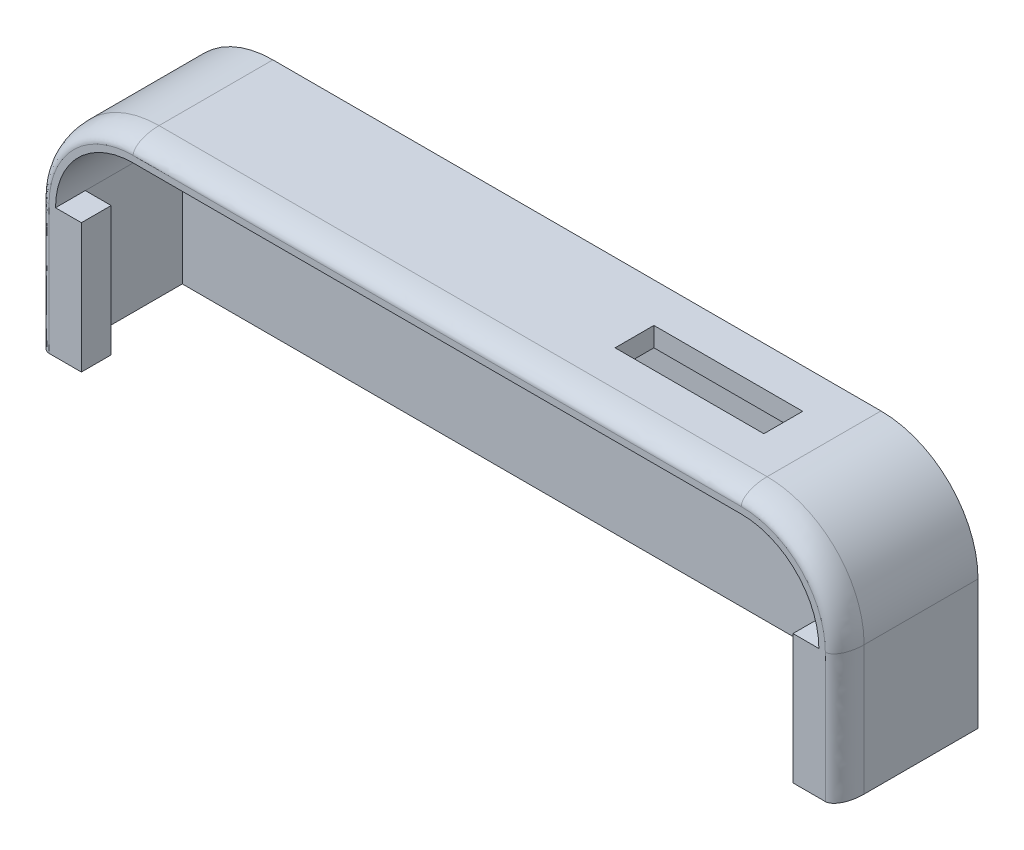
SolidWorks part; units mm, degrees
ref_plane "Front Plane" through (0, 0, 0) normal (0, 0, 1) x (1, 0, 0)
ref_plane "Top Plane" through (0, 0, 0) normal (0, 1, 0) x (1, 0, 0)
ref_plane "Right Plane" through (0, 0, 0) normal (1, 0, 0) x (0, 0, -1)
sketch "Sketch1" plane through (0, 0, 0) normal (0, 0, 1) x (1, 0, 0)
  line L0 (31, 17.5) -> (31, 0)
  line L1 (0, 0) -> (62, 0)
  line L2 (0, 0) -> (0, 10)
  line L3 (7.5, 17.5) -> (54.5, 17.5)
  line L4 (62, 0) -> (62, 10)
  line L5 (7.5, 16) -> (54.5, 16)
  line L9 (1.5, 0) -> (1.5, 10)
  line L12 (60.5, 10) -> (60.5, 0)
  arc A0 (0, 10) -> (7.5, 17.5) centre (7.5, 10) cw
  arc A1 (62, 10) -> (54.5, 17.5) centre (54.5, 10) ccw
  arc A2 (1.5, 10) -> (7.5, 16) centre (7.5, 10) cw
  arc A3 (60.5, 10) -> (54.5, 16) centre (54.5, 10) ccw
  dimension "D5" = 1.5
extrude "Boss-Extrude1" add sketch "Sketch1" along normal blind 10.8 contours L9 A2 L5 L0 L3 A0 L2 L1 | A3 L12 L1 L4 A1 L3 L0 L5 region at (42.75, 17.144, 0) region at (30.644, 16.75, 0)
sketch "Sketch2" plane through (0, 0, 0) normal (0, 0, -1) x (-1, 0, 0)
  line L0 (-1.5, 0) -> (-1.5, 10)
  line L1 (-7.5, 16) -> (-54.5, 16)
  line L2 (-60.5, 0) -> (-60.5, 10)
  line L3 (-60.5, 0) -> (-1.5, 0)
  arc A0 (-1.5, 10) -> (-7.5, 16) centre (-7.5, 10) ccw
  arc A1 (-54.5, 16) -> (-60.5, 10) centre (-54.5, 10) ccw
extrude "Boss-Extrude2" add sketch "Sketch2" against normal blind 1 separate body
combine bodies "Combine1" operation type add bodies to combine 102 101
sketch "Sketch3" plane through (0, 0, 10.8) normal (0, 0, 1) x (1, 0, 0)
  line L0 (0, 0) -> (3.5, 0)
  line L1 (0, 0) -> (0, 10)
  line L2 (0, 0) -> (0, 10) construction
  line L3 (3.5, 0) -> (3.5, 10)
  line L4 (3.5, 10) -> (0, 10)
  line L5 (1.5, 10) -> (1.5, 0)
  line L6 (31, 16) -> (31, -7.5027)
  line L7 (7.5, 16) -> (54.5, 16) construction
  line L8 (60.5, 10) -> (60.5, 0)
  line L9 (62, 0) -> (58.5, 0)
  line L10 (58.5, 10) -> (62, 10)
  line L11 (58.5, 0) -> (58.5, 10)
  line M7 (1.5, 0) -> (1.5, 10)
  line M11 (60.5, 10) -> (60.5, 0)
  dimension "D1" = 3.5
  dimension "D2" = 10
extrude "Boss-Extrude3" add sketch "Sketch3" against normal blind 2.3 contours L3 L4 L0 M7 | L11 L9 L10 M11 region at (2.5, 5, 10.8) region at (59.5, 5, 10.8)
fillet "Fillet1" radius 1 5 edges at (0, 5, 10.8) (62, 5, 10.8) (2.1967, 15.3033, 10.8) (59.8033, 15.3033, 10.8) (31, 17.5, 10.8) second distance 2 first distance on face at (31, 9.4708, 10.8)
sketch "Sketch4" plane through (0, 17.5, 0) normal (0, 1, 0) x (1, 0, 0)
  line L0 (62, -8.8) -> (62, 0) construction
  line L1 (51.5, -6.05) -> (40, -6.05)
  line L2 (51.5, -6.05) -> (51.5, -3.05)
  line L3 (51.5, -3.05) -> (40, -3.05)
  line L4 (40, -6.05) -> (40, -3.05)
  line L5 (7.5, 0) -> (54.5, 0) construction
  dimension "D1" = 10.5
  dimension "D2" = 11.5
  dimension "D3" = 3.05
  dimension "D4" = 3
extrude "Cut-Extrude1" cut sketch "Sketch4" against normal up to next
